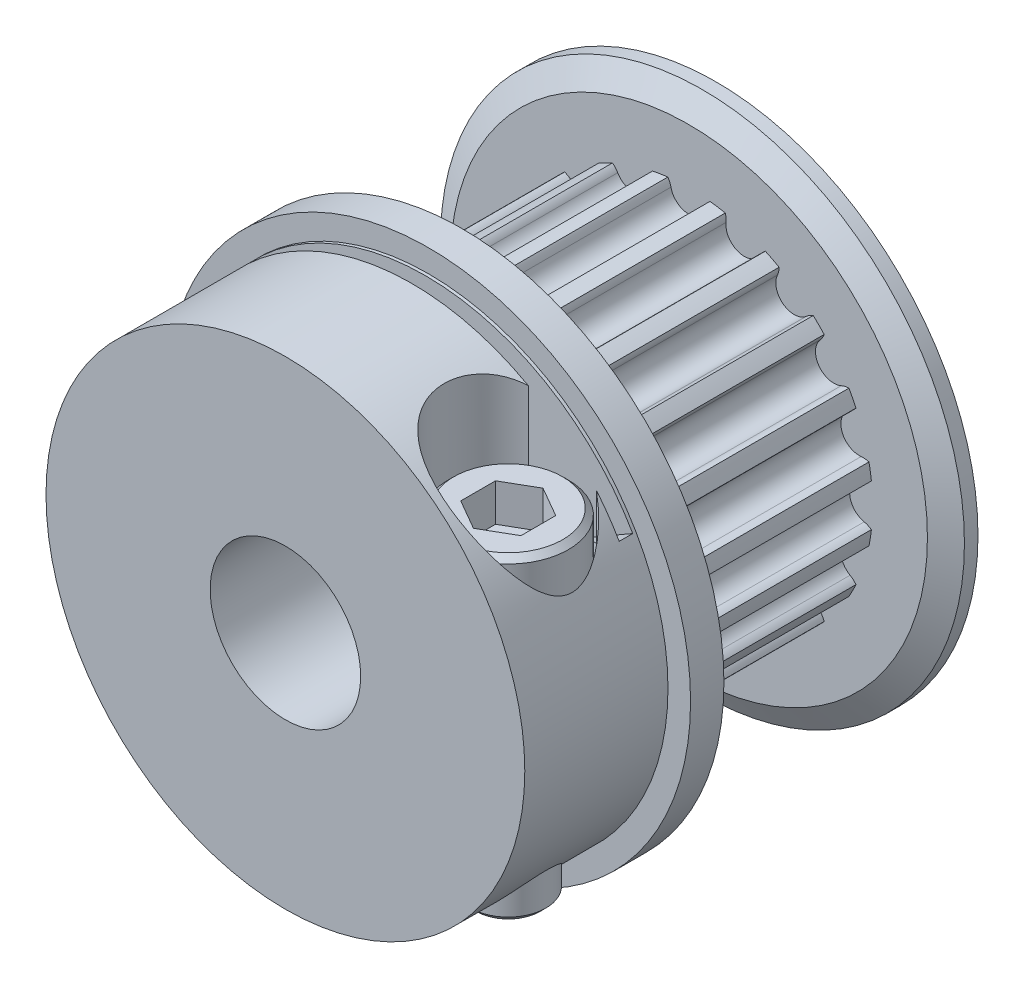
SolidWorks part; units mm, degrees
ref_plane "Front Plane" through (0, 0, 0) normal (0, 0, 1) x (1, 0, 0)
ref_plane "Top Plane" through (0, 0, 0) normal (0, 1, 0) x (1, 0, 0)
ref_plane "Right Plane" through (0, 0, 0) normal (1, 0, 0) x (0, 0, -1)
ref_plane "Plane1" through (0, 0, 0) normal (1, 0, 0) x (0, 0, -1)
sketch "Sketch1" plane through (0, 0, 0) normal (1, 0, 0) x (0, 0, -1)
  line L0 (-6, 7.95) -> (-6, 2.5)
  line L1 (-6, 2.5) -> (0, 2.5)
  line L2 (0, 2.5) -> (0, 7.95)
  line L3 (0, 7.95) -> (-6, 7.95)
  line L4 (-6.3, 0) -> (0.3, 0) construction
  dimension "D1" = 6
revolve "Revolve1" add sketch "Sketch1" angle 360 about L4
ref_plane "Plane2" through (0, 0, 0) normal (-0.5, 0.866, 0) x (0, 0, -1)
sketch "Sketch2" plane through (0, 0, 0) normal (-0.5, 0.866, 0) x (0, 0, -1)
  line L0 (-1.8, 7.95) -> (-1.8, 2.5)
  line L1 (-1.8, 2.5) -> (-1.35, 2.5)
  line L2 (-1.35, 2.5) -> (-1.35, 7.95)
  line L3 (-1.35, 7.95) -> (-1.8, 7.95)
  line L4 (-1.8225, 0) -> (-1.3275, 0) construction
  dimension "D1" = 0.45
revolve "Cut-Revolve1" cut sketch "Sketch2" angle 180 about L4
ref_plane "Plane3" through (0, 0, 0) normal (1, 0, 0) x (0, 0, -1)
sketch "Sketch3" plane through (0, 0, 0) normal (1, 0, 0) x (0, 0, -1)
  line L0 (-1.35, 0.5) -> (-6, -3.4018)
ref_plane "Plane4" through (0, 0, 3.6) normal (0, 0, 1) x (1, 0, 0)
sketch "Sketch4" plane through (0, 0, 3.6) normal (0, 0, 1) x (1, 0, 0)
  line L0 (2.875, 7.4119) -> (2.875, 2.385)
  line L1 (2.875, 2.385) -> (3.7375, 2.385)
  line L2 (3.7375, 2.385) -> (3.7375, -7.0167)
  line L3 (3.7375, -7.0167) -> (5, -7.0167)
  line L4 (5, -7.0167) -> (5, 7.4119)
  line L5 (5, 7.4119) -> (2.875, 7.4119)
  line L6 (5, -7.7381) -> (5, 8.1334) construction
revolve "Cut-Revolve2" cut sketch "Sketch4" angle 360 about L6 reverse direction yes
ref_plane "Plane5" through (5, 0, 3.6) normal (0, 0, 1) x (1, 0, 0)
sketch "Sketch5" plane through (5, 0, 3.6) normal (0, 0, 1) x (1, 0, 0)
  line L0 (2, 4.6945) -> (2, 2.385)
  line L1 (2, 2.385) -> (1.25, 2.385)
  line L2 (1.25, 2.385) -> (1.25, -5.9903)
  line L3 (1.0595, -6.1808) -> (0, -6.1808)
  line L4 (0, -6.1808) -> (0, 4.885)
  line L5 (0, 4.885) -> (1.8095, 4.885)
  line L6 (1.8095, 4.885) -> (2, 4.6945)
  line L7 (1.25, -5.9903) -> (1.0595, -6.1808)
  line L8 (0, -6.7341) -> (0, 5.4383) construction
  dimension "D1" = 2.5
revolve "Revolve2" add sketch "Sketch5" angle 360 about L8
sketch "Sketch6" plane through (0, 4.885, 0) normal (0, 1, 0) x (-1, 0, 0)
  line L0 (-5, 2.4453) -> (-4, 3.0226)
  line L1 (-4, 3.0226) -> (-4, 4.1774)
  line L2 (-4, 4.1774) -> (-5, 4.7547)
  line L3 (-5, 4.7547) -> (-6, 4.1774)
  line L4 (-6, 4.1774) -> (-6, 3.0226)
  line L5 (-6, 3.0226) -> (-5, 2.4453)
  line L6 (-5, 2.3298) -> (-5, 4.8702) construction
  dimension "D1" = 2
extrude "Cut-Extrude1" cut sketch "Sketch6" against normal blind 1.25
ref_plane "Plane6" through (0, 0, 0) normal (0, 0, -1) x (-1, 0, 0)
sketch "Sketch7" plane through (0, 0, 0) normal (0, 0, -1) x (-1, 0, 0)
  circle A0 centre (0, 0) radius 2.5
  circle A1 centre (0, 0) radius 6.1
  dimension "D1" = 5
  dimension "D2" = 12.2
extrude "Boss-Extrude1" add sketch "Sketch7" along normal blind 7.4
ref_plane "Plane7" through (0, 0, 0) normal (0, 0, 1) x (0.9511, -0.309, 0)
sketch "Sketch8" plane through (0, 0, 0) normal (0, 0, 1) x (0.9511, -0.309, 0)
  arc A0 (-0.5962, 5.8206) -> (0.5962, 5.8206) centre (0, 5.9476) ccw
  arc A1 (0.6997, 6.0597) -> (0.5962, 5.8206) centre (1.2421, 5.683) ccw
  arc A2 (-0.5962, 5.8206) -> (-0.6997, 6.0597) centre (-1.2421, 5.683) ccw
  arc A3 (0.6997, 6.0597) -> (-0.6997, 6.0597) centre (0, 0) ccw
extrude "Cut-Extrude2" cut sketch "Sketch8" against normal blind 7.4
ref_plane "Plane8" through (0, 0, 0) normal (-1, 0, 0) x (0, 0, 1)
ref_plane "Plane9" through (0, 0, 0) normal (0, -1, 0) x (0, 0, 1)
ref_axis "Axis1" through (0, 0, -80.9) along (0, 0, 1)
pattern_circular "CirPattern1" count 20 every 18 about axis through (0, 0, -80.9) along (0, 0, 1) of "Cut-Extrude2"
ref_plane "Plane10" through (0, 0, 0) normal (1, 0, 0) x (0, 0, -1)
sketch "Sketch9" plane through (0, 0, 0) normal (1, 0, 0) x (0, 0, -1)
  line L0 (7.4, 2.5) -> (7.4, 7.9206)
  line L1 (7.4, 7.9206) -> (7.85, 8.7)
  line L2 (7.85, 8.7) -> (8.3, 8.7)
  line L3 (8.3, 8.7) -> (7.85, 7.9206)
  line L4 (7.85, 7.9206) -> (7.85, 2.5)
  line L5 (7.85, 2.5) -> (7.4, 2.5)
  line L6 (-0.415, 0) -> (8.715, 0) construction
  point P6 (0, 0)
  dimension "D1" = 0.45
revolve "Revolve3" add sketch "Sketch9" angle 360 about L6
sketch "Sketch10" plane through (0, 0, -7.85) normal (0, 0, -1) x (-1, 0, 0)
  circle A0 centre (0, 0) radius 2.5
  circle A1 centre (0, 0) radius 5.49
extrude "Boss-Extrude2" add sketch "Sketch10" along normal blind 0.45
sketch "Sketch11" plane through (0, 0, -8.3) normal (0, 0, -1) x (-1, 0, 0)
  circle A0 centre (0, 0) radius 4.3
extrude "Cut-Extrude-Thin1" cut sketch "Sketch11" against normal blind 0.0508 thin thin type mid plane wall 0.0508
ref_plane "Plane11" through (0, 0, 0) normal (1, 0, 0) x (0, 0, -1)
sketch "Sketch12" plane through (0, 0, 0) normal (1, 0, 0) x (0, 0, -1)
  line L0 (0, 2.5) -> (0, 7.9206)
  line L1 (0, 7.9206) -> (-0.1374, 8.7)
  line L2 (-0.1374, 8.7) -> (-1.245, 8.7)
  line L3 (-1.245, 8.7) -> (-1.245, 2.5)
  line L4 (-1.245, 2.5) -> (0, 2.5)
  line L5 (-1.6773, 0) -> (7.8322, 0) construction
  point P0 (0, 0)
  dimension "D1" = 1.245
revolve "Revolve4" add sketch "Sketch12" angle 360 about L5
